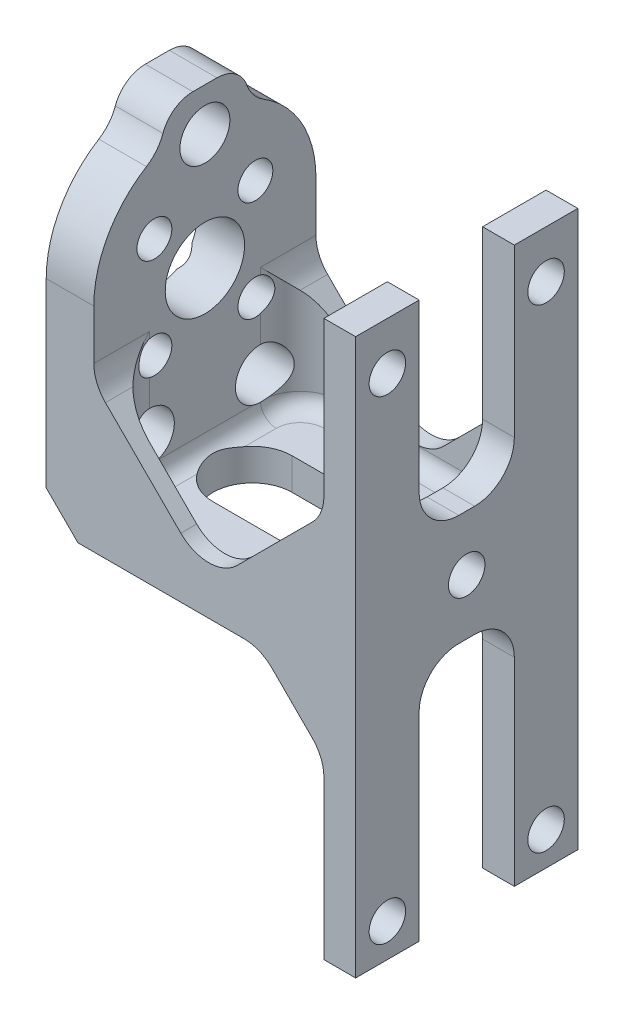
SolidWorks part; units mm, degrees
material "6061-T6 (SS)"
ref_plane "Front Plane" through (0, 0, 0) normal (0, 0, 1) x (1, 0, 0)
ref_plane "Top Plane" through (0, 0, 0) normal (0, 1, 0) x (1, 0, 0)
ref_plane "Right Plane" through (0, 0, 0) normal (1, 0, 0) x (0, 0, -1)
sketch "Sketch1" plane through (0, 0, 0) normal (0, 1, 0) x (1, 0, 0)
  line L0 (-7.25, 7) -> (7.25, -7) construction
  line L1 (-7.25, 7) -> (7.25, 7)
  line L2 (-7.25, 7) -> (-7.25, -7)
  line L3 (-7.25, -7) -> (7.25, -7)
  line L4 (7.25, 7) -> (7.25, -7)
  dimension "D2" = 14.5
  dimension "D1" = 14
extrude "base" add sketch "Sketch1" along normal blind 2
sketch "Sketch3" plane through (0, 0, 7) normal (0, 0, 1) x (1, 0, 0)
  line L0 (-7.25, 2) -> (7.25, 2) construction
  line L1 (-7.25, 0) -> (-10.25, 0)
  line L2 (-7.25, 0) -> (-7.25, 19)
  line L3 (-7.25, 19) -> (-10.25, 19)
  line L4 (-10.25, 0) -> (-10.25, 19)
  dimension "D1" = 3
  dimension "D2" = 17
extrude "motorFlange" add sketch "Sketch3" against normal up to surface (14 mm away) up to face at (0, 1, -7)
hole_wizard "CSK for M2 Flat Head Machine Screw1" positions "Sketch6" profile "Sketch7" countersink size "M2" standard "ANSI Metric"
sketch "Sketch6" plane through (-10.25, 0, 0) normal (-1, 0, 0) x (0, 0, 1)
  line L1 (-3.182, 15.182) -> (3.182, 15.182)
  line L2 (-3.182, 15.182) -> (-3.182, 8.818)
  line L3 (-3.182, 8.818) -> (3.182, 8.818)
  line L4 (3.182, 15.182) -> (3.182, 8.818)
  line L5 (0, 15.182) -> (0, 19)
  line L7 (-7, 19) -> (7, 19) construction
  line L8 (-3.182, 15.182) -> (3.182, 8.818) construction
  point P0 (-3.182, 15.182)
  point P2 (-3.182, 8.818)
  point P4 (3.182, 8.818)
  point P6 (3.182, 15.182)
  point P121 (0, 19)
  point P129 (0, 12)
  dimension "D3" = 7
  dimension "D1" = 9
sketch "Sketch7" plane through (-10.25, 15.182, -3.182) normal (0, 1, 0) x (0, 0, 1)
  line L0 (0, 0) -> (0, 5.8609)
  line L1 (0, 5.8609) -> (1.1, 5.2)
  line L2 (1.1, 5.2) -> (1.1, 1.1)
  line L3 (1.1, 1.1) -> (2.2, 0)
  line L5 (2.2, 0) -> (0, 0)
  line L6 (-1.1, 1.1) -> (-2.2, 0) construction
  line L10 (0, 5.8609) -> (-1.1, 5.2) construction
  line L11 (0, -6.35) -> (0, 107.95) construction
  dimension "Hole Dia." = 2.2
  dimension "Hole Depth" = 5.2
  dimension "Near C'Sink Dia." = 4.4
  dimension "Near C'Sink Angle" = 90
  dimension "Drill Angle" = 118
sketch "Sketch16" plane through (-10.25, 0, 0) normal (-1, 0, 0) x (0, 0, 1)
  line L0 (-3.182, 15.182) -> (3.182, 8.818) construction
  circle A0 centre (0, 12) radius 2.5
  dimension "D1" = 5
extrude "Cut-Extrude1" cut sketch "Sketch16" against normal blind 10
sketch "Sketch17" plane through (0, 19, 0) normal (0, 1, 0) x (1, 0, 0)
  line L0 (-7.25, 7) -> (-7.25, -7) construction
  line L1 (-10.25, 7) -> (-10.25, -7) construction
  line L2 (-7.25, -2.5) -> (-10.25, -2.5)
  line L3 (-7.25, -2.5) -> (-7.25, 2.5)
  line L4 (-7.25, 2.5) -> (-10.25, 2.5)
  line L5 (-10.25, -2.5) -> (-10.25, 2.5)
  point P8 (-7.25, 0)
  dimension "D1" = 5
extrude "Boss-Extrude5" add sketch "Sketch17" along normal blind 3
sketch "Sketch18" plane through (0, 2, 0) normal (0, 1, 0) x (1, 0, 0)
  line L0 (-7.25, 7) -> (-7.25, -7) construction
  line L1 (-7.25, 2.5) -> (-2.25, 2.5)
  line L2 (-7.25, 2.5) -> (-7.25, -2.5)
  line L3 (-7.25, -2.5) -> (-2.25, -2.5)
  line L4 (-2.25, 2.5) -> (-2.25, -2.5)
  point P6 (-7.25, 0)
  dimension "D1" = 5
  dimension "D2" = 5
extrude "Cut-Extrude2" [suppressed] cut sketch "Sketch18" against normal through all both and the other way through all
sketch "Sketch23" plane through (0, 0, 7) normal (0, 0, 1) x (1, 0, 0)
  line L0 (-10.25, 0) -> (10.554, -20.804) construction
  line L1 (-10.25, 0) -> (7.25, 0) construction
  dimension "D1" = 45
sketch "Sketch4" plane through (0, 0, 7) normal (0, 0, 1) x (1, 0, 0)
  line L1 (7.25, 0) -> (9.25, 0)
  line L2 (7.25, 0) -> (7.25, 7)
  line L3 (7.25, 7) -> (9.25, 7)
  line L4 (9.25, 0) -> (9.25, 7)
  line L5 (-7.25, 2) -> (7.25, 2) construction
  dimension "D1" = 2
  dimension "D2" = 5
extrude "Boss-Extrude3" add sketch "Sketch4" against normal up to surface (14 mm away) up to face at (-3.4167, 7, -7)
sketch "Sketch13" plane through (0, 7, 0) normal (0, 1, 0) x (1, 0, 0)
  line L0 (7.25, 7) -> (7.25, -7) construction
  line L1 (9.25, -7) -> (7.25, -7)
  line L2 (9.25, -7) -> (9.25, -3)
  line L3 (9.25, -3) -> (7.25, -3)
  line L4 (7.25, -7) -> (7.25, -3)
  dimension "D1" = 4
extrude "Boss-Extrude4" add sketch "Sketch13" along normal blind 13
mirror "Mirror5" about plane through (0, 0, 0) normal (0, 0, 1) of "Boss-Extrude4"
sketch "Sketch22" plane through (0, 0, 0) normal (0, -1, 0) x (1, 0, 0)
  line L1 (9.25, 7) -> (7.25, 7)
  line L2 (9.25, 7) -> (9.25, 3)
  line L3 (9.25, 3) -> (7.25, 3)
  line L4 (7.25, 7) -> (7.25, 3)
  line L5 (9.25, -7) -> (7.25, -7)
  line L6 (9.25, -7) -> (9.25, -3)
  line L7 (9.25, -3) -> (7.25, -3)
  line L8 (7.25, -7) -> (7.25, -3)
extrude "Boss-Extrude6" add sketch "Sketch22" along normal blind 15
sketch "Sketch26" plane through (0, 0, 7) normal (0, 0, 1) x (1, 0, 0)
  line L0 (-7.25, 9.25) -> (0, 2)
  line L1 (-7.25, 2) -> (-7.25, 19) construction
  line L2 (-7.25, 2) -> (7.25, 2) construction
  dimension "D1" = 45
rib "Rib3" sketch "Sketch26" sketch "Sketch26" thickness 1 extrusion direction parallel to sketch draft on no parameters "D1"=1
sketch "Sketch27" plane through (0, 0, 7) normal (0, 0, 1) x (1, 0, 0)
  line L0 (0, 2) -> (7.25, 9.25)
  line L1 (7.25, 20) -> (7.25, 2) construction
rib "Rib4" sketch "Sketch27" sketch "Sketch27" thickness 1 extrusion direction parallel to sketch draft on no parameters "D1"=1
sketch "Sketch28" plane through (0, 0, 7) normal (0, 0, 1) x (1, 0, 0)
  line L0 (3.25, 0) -> (7.25, -4)
  line L1 (-10.25, 0) -> (7.25, 0) construction
  line L2 (7.25, -15) -> (7.25, 0) construction
  dimension "D1" = 45
  dimension "D2" = 4
rib "Rib7" sketch "Sketch28" sketch "Sketch28" thickness 1 extrusion direction parallel to sketch draft on no parameters "D1"=1
mirror "Mirror7" about plane through (0, 0, 0) normal (0, 0, 1) of "Rib7", "Rib4", "Rib3"
fillet "Fillet5" radius 2.5 2 edges at (-8.75, 19, 2.5) (-8.75, 19, -2.5)
fillet "Fillet1" radius 7 2 edges at (-8.75, 19, -7) (-8.75, 19, 7)
fillet "Fillet6" radius 2 2 edges at (-8.75, 22, 2.5) (-8.75, 22, -2.5)
fillet "Fillet4" radius 2.5 2 edges at (8.25, 7, -3) (8.25, 7, 3)
fillet "Fillet8" radius 2.5 8 edges at (8.25, 0, -3) (8.25, 0, 3) (7.25, -4, -6.5) (3.25, 0, -6.5) (7.25, -4, 6.5) (3.25, 0, 6.5) (7.25, -2, 6) (7.25, -2, -6)
fillet "Fillet7" radius 1 6 edges at (7.25, 0, -2) (7.25, 0, 2) (3.4822, 0, -6) (3.4822, 0, 6) (6.5178, 0, 5.2678) (6.5178, 0, -5.2678)
fillet "Fillet13" radius 2.5 10 edges at (0, 2, 6.5) (-7.25, 9.25, 6.5) (-7.25, 5.625, 6) (-7.25, 5.625, -6) (7.25, 5.625, -6) (7.25, 5.625, 6) (7.25, 9.25, 6.5) (7.25, 9.25, -6.5) (-7.25, 9.25, -6.5) (0, 2, -6.5)
fillet "Fillet11" radius 1 10 edges at (7.25, 2, 0) (-7.25, 2, 0) (-6.5178, 2, 5.2678) (-6.5178, 2, -5.2678) (-2.375, 2, 6) (2.375, 2, 6) (2.375, 2, -6) (-2.375, 2, -6) (6.5178, 2, -5.2678) (6.5178, 2, 5.2678)
sketch "Sketch21" plane through (0, 2, 0) normal (0, 1, 0) x (1, 0, 0)
  line L1 (-7.25, -3.5) -> (-7.25, 3.5) construction
  circle A0 centre (-3.75, 0) radius 2.5
  point P5 (-7.25, 0)
  point P6 (-6.25, 0)
  dimension "D1" = 5
  dimension "D2" = 1
extrude "wireHole" [suppressed] cut sketch "Sketch21" against normal through all both and the other way through all
sketch "Sketch25" plane through (0, 2, 0) normal (0, 1, 0) x (1, 0, 0)
  line L0 (-4.25, 0) -> (0.75, 0) construction
  line L1 (-4.25, 2.5) -> (0.75, 2.5)
  line L2 (-4.25, -2.5) -> (0.75, -2.5)
  line L3 (-7.25, -3.5) -> (-7.25, 3.5) construction
  arc A0 (-4.25, 2.5) -> (-4.25, -2.5) centre (-4.25, 0) ccw
  arc A1 (0.75, -2.5) -> (0.75, 2.5) centre (0.75, 0) ccw
  point P3 (-1.75, 0)
  point P8 (-6.75, 0)
  point P13 (-7.25, 0)
  dimension "D2" = 5
  dimension "D3" = 2.5
  dimension "D1" = 0.5
extrude "wireSlot" cut sketch "Sketch25" against normal through all both and the other way through all
chamfer "Chamfer1" distance 2 angle 45 1 edges at (-10.25, 0, 0)
hole_wizard "Tapped Hole for M2.2x0.45 Helicoil1" positions "Sketch14" profile "Sketch15" tap size "M2.2x0.45" standard "Helicoil® Metric"
sketch "Sketch14" plane through (9.25, 0, 0) normal (1, 0, 0) x (0, 0, -1)
  line L0 (-5, 20) -> (-5, 17) construction
  line L1 (-7, 20) -> (-3, 20) construction
  line L3 (0, 7) -> (0, 0) construction
  line L6 (0.5, 0) -> (-0.5, 0) construction
  line L7 (-5, 17) -> (-7, 17) construction
  line L8 (-7, -15) -> (-7, 20) construction
  line L16 (-5, -15) -> (-5, -12.9) construction
  line L17 (-3, -15) -> (-7, -15) construction
  line L18 (0.5, 7) -> (-0.5, 7) construction
  point P0 (-5, 17)
  point P41 (0, 3.5)
  point P42 (5, 17)
  point P54 (-5, -12.9)
  point P60 (5, -12.9)
  dimension "D1" = 32
  dimension "D2" = 2.1
sketch "Sketch15" plane through (9.25, 17, 5) normal (0, 1, 0) x (0, 0, -1)
  line L0 (0, 0) -> (0, 6.691)
  line L1 (0, 6.691) -> (1.15, 6)
  line L2 (1.15, 6) -> (1.15, 0)
  line L5 (1.15, 0) -> (0, 0)
  line L10 (0, 6.691) -> (-1.15, 6) construction
  line L11 (0, -6.35) -> (0, 107.95) construction
  dimension "Tap Drill Dia." = 2.3
  dimension "Tap Drill Depth" = 6
  dimension "Drill Angle" = 118
cosmetic thread "Hole Thread7" parameters "D1"=2, "D2"=2.845
cosmetic thread "Hole Thread8" parameters "D1"=2.7, "D2"=2.845
cosmetic thread "Hole Thread9" parameters "D1"=2.7, "D2"=2.845
cosmetic thread "Hole Thread11" parameters "D1"=2.7, "D2"=2.845
cosmetic thread "Hole Thread12" parameters "D1"=2.7, "D2"=2.845
hole_wizard "Tapped Hole for M3x0.5 Helicoil1" positions "Sketch11" profile "Sketch12" tap size "M3x0.5" standard "Helicoil® Metric"
sketch "Sketch11" plane through (-10.25, 0, 0) normal (-1, 0, 0) x (0, 0, 1)
  line L0 (0, 0) -> (0, 19.2948) construction
  line L1 (-7, 0) -> (7, 0) construction
  line L2 (1.8358, 16.922) -> (0, 19.2948) construction
  line L4 (3.0416, 17.855) -> (0.6299, 15.9891) construction
  arc A0 (2.1803, 13.2233) -> (1.2233, 14.1803) centre (3.182, 15.182) ccw construction
  point P0 (3.5, 4.5)
  point P4 (0, 19.2948)
  point P16 (-3.5, 4.5)
  point P33 (1.8358, 16.922)
  dimension "D1" = 7
  dimension "D2" = 3
  dimension "D3" = 4.5
cosmetic thread "Hole Thread2" parameters "D1"=3.5, "D2"=3.716
cosmetic thread "Hole Thread3" parameters "D1"=3.5, "D2"=3.716
sketch "Sketch12" plane through (-10.25, 4.5, 3.5) normal (0, 1, 0) x (0, 0, 1)
  line L0 (0, 0) -> (0, 8.4464)
  line L1 (0, 8.4464) -> (1.575, 7.5)
  line L2 (1.575, 7.5) -> (1.575, 0)
  line L5 (1.575, 0) -> (0, 0)
  line L10 (0, 8.4464) -> (-1.575, 7.5) construction
  line L11 (0, -6.35) -> (0, 107.95) construction
  dimension "Tap Drill Dia." = 3.15
  dimension "Tap Drill Depth" = 7.5
  dimension "Drill Angle" = 118
cosmetic thread "Hole Thread10" parameters "D1"=3, "D2"=3.716
sketch "Sketch29" plane through (0, 20, 0) normal (0, 1, 0) x (1, 0, 0)
  line L4 (9.25, -7) -> (9.25, -3)
  line L5 (9.25, -3) -> (7.25, -3)
  line L6 (7.25, -3) -> (7.25, -7)
  line L7 (7.25, -7) -> (9.25, -7)
  line L8 (9.25, -7) -> (9.25, -3)
  line L9 (9.25, -3) -> (7.25, -3)
  line L10 (7.25, -3) -> (7.25, -7)
  line L11 (7.25, -7) -> (9.25, -7)
  line L12 (9.25, 7) -> (7.25, 7)
  line L13 (7.25, 7) -> (7.25, 3)
  line L14 (7.25, 3) -> (9.25, 3)
  line L15 (9.25, 3) -> (9.25, 7)
  line L16 (9.25, 7) -> (7.25, 7)
  line L17 (7.25, 7) -> (7.25, 3)
  line L18 (7.25, 3) -> (9.25, 3)
  line L19 (9.25, 3) -> (9.25, 7)
  dimension "D1" = 0
  dimension "D2" = 0
extrude "Boss-Extrude7" [suppressed] add sketch "Sketch29" along normal blind 20
equation "\"motorDiameter\"= 14mm"
equation "\"baseThickness\"= 2mm"
equation "\"motorWallThickness\"= 3mm"
equation "\"boardWallThickness\"= \"baseThickness\""
equation "\"D1@base\" = \"baseThickness\""
equation "\"motorLength\"= 12.5mm"
equation "\"magnetHeight\"= 2mm"
equation "\"rotorClearance\"= 3mm"
equation "\"D1@Sketch3\"=\"motorWallThickness\""
equation "\"D2@Sketch3\"=\"motorDiameter\"+\"rotorClearance\""
equation "\"D1@Sketch4\"=\"boardWallThickness\""
equation "\"D1@Fillet1\"=\"motorDiameter\"/2"
equation "\"D3@Sketch6\"=\"motorDiameter\"/2"
equation "\"encoderClearance\"= 5mm"
equation "\"D2@Sketch4\"=\"motorDiameter\"/2+\"rotorClearance\"-\"encoderClearance\""
equation "\"cutterOD\"= 5mm"
equation "\"cutterSnubRadius\"= 1mm"
equation "\"D1@Fillet4\"= \"cutterOD\" / 2"
equation "\"D1@Sketch1\"=\"motorDiameter\""
equation "\"encoderClearance_vertical\"= 1mm"
equation "\"encoderHeight\"= 1mm"
equation "\"encoderWidth\"= 2mm"
equation "\"D2@Sketch1\"=\"motorLength\"+\"magnetHeight\"+\"encoderHeight\"+\"encoderClearance_vertical\"-\"boardWallThickness\""
equation "\"D1@Fillet5\"=\"cutterOD\"/2"
equation "\"D1@Fillet8\"=\"cutterOD\"/2"
equation "\"D1@Fillet11\"=\"cutterSnubRadius\""
equation "\"D1@Fillet7\"=\"cutterOD\"/2"
equation "\"D3@Sketch25\"=\"cutterOD\"/2"
equation "\"D1@Fillet7\"=\"cutterSnubRadius\"+0"
equation "\"D1@Fillet13\"=\"cutterOD\"/2"
